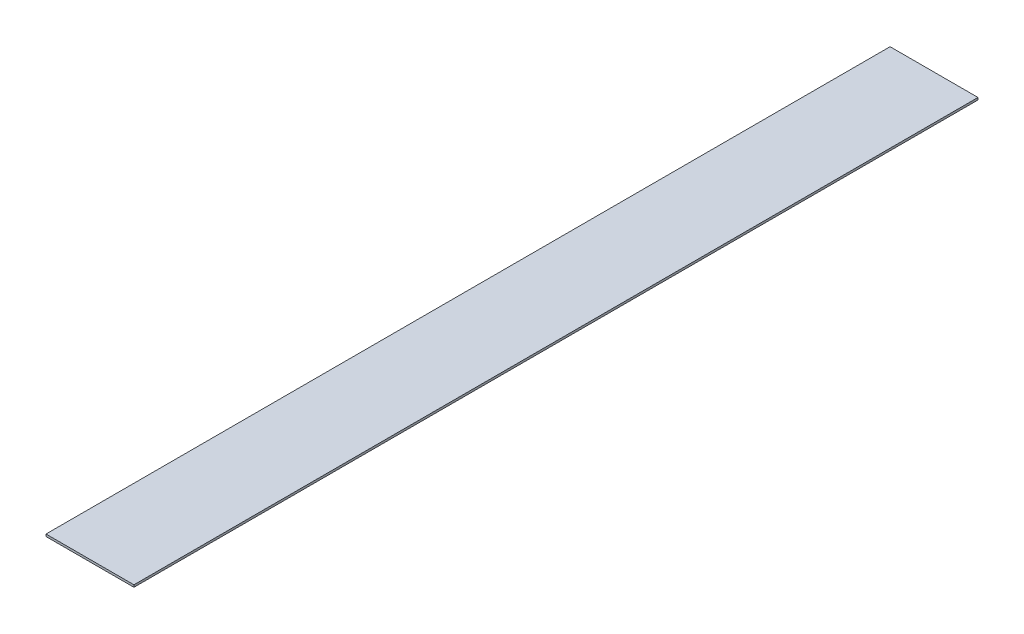
SolidWorks part; units mm, degrees
note: '?' marks a value the reader was unsure of.
ref_plane "Спереди" through (0, 0, 0) normal (0, 0, 1) x (1, 0, 0)
ref_plane "Сверху" through (0, 0, 0) normal (0, 1, 0) x (1, 0, 0)
ref_plane "Справа" through (0, 0, 0) normal (1, 0, 0) x (0, 0, -1)
sketch "Эскиз1" plane through (0, 0, 0) normal (0, 0, 1) x (1, 0, 0)
  line L1 (-100, 2.5) -> (100, 2.5)
  line L2 (-100, 2.5) -> (-100, -2.5)
  line L3 (-100, -2.5) -> (100, -2.5)
  line L4 (100, 2.5) -> (100, -2.5)
  line L5 (-100, 2.5) -> (100, -2.5) construction
  line L6 (-100, -2.5) -> (100, 2.5) construction
  point P0 (0, 0)
  dimension "D1" = 5
  dimension "D2" = 200
extrude "Бобышка-Вытянуть1" add sketch "Эскиз1" along normal mid plane 1920
sketch "Эскиз2" plane through (0, -2.5, 0) normal (0, -1, 0) x (1, 0, 0)
  line L0 (0, 960) -> (0, -960) construction
  line L1 (-100, 960) -> (100, 960) construction
  line L2 (-100, -960) -> (100, -960) construction
  line L3 (-100, 0) -> (98.6926, 0) construction
  line L4 (-100, 960) -> (-100, -960) construction
ref_axis "Ось1" through (0, -50, 0) along (0, 1, 0)?
